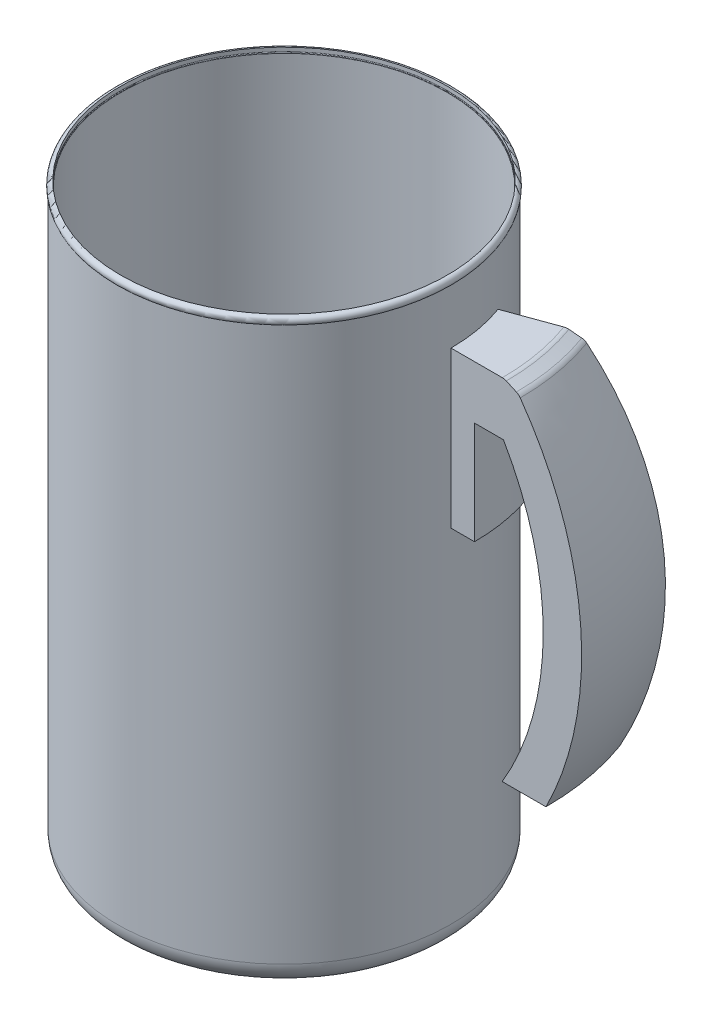
SolidWorks part; units mm, degrees
ref_plane "Front Plane" through (0, 0, 0) normal (0, 0, 1) x (1, 0, 0)
ref_plane "Top Plane" through (0, 0, 0) normal (0, 1, 0) x (1, 0, 0)
ref_plane "Right Plane" through (0, 0, 0) normal (1, 0, 0) x (0, 0, -1)
sketch "Sketch1" plane through (0, 0, 0) normal (0, 0, 1) x (1, 0, 0)
  line L0 (0, 0) -> (0, 316.8923) construction
  line L1 (0, 15.1909) -> (-75, 15.1909)
  line L2 (-85, 25.1909) -> (-85, 314.4808)
  line L3 (-85.1655, 314.6463) -> (-85.1844, 314.6463)
  line L4 (0, 15.1909) -> (0, 315.1909)
  line L5 (-85.1844, 315.1909) -> (0, 315.1909)
  arc A0 (-85.1844, 315.1909) -> (-85.1844, 314.6463) centre (-85.1844, 314.9186) ccw
  arc A1 (-85.1655, 314.6463) -> (-85, 314.4808) centre (-85.1655, 314.4808) cw
  arc A2 (-75, 15.1909) -> (-85, 25.1909) centre (-75, 25.1909) cw
  point P6 (-85.1821, 314.6461)
  dimension "D3" = 10
  dimension "D1" = 170
  dimension "D4" = 300
revolve "Revolve1" add sketch "Sketch1" angle 360 about L4
shell "Shell7" thickness 2 removed face at (0, 315.1909, -85.1844) outward yes
sketch "Sketch4" plane through (0, 0, 0) normal (0, 0, 1) x (1, 0, 0)
  line L0 (87, 285.1658) -> (113.7412, 285.1658)
  line L1 (87, 25.1909) -> (87, 313.5522) construction
  line L2 (115.793, 284.7255) -> (121.0361, 282.3661)
  line L3 (87, 203.914) -> (99.2279, 203.914)
  line L4 (99.2279, 203.914) -> (99.2279, 257.4468)
  line L5 (99.2279, 257.4468) -> (114.2959, 257.4468)
  line L6 (113.6555, 102.9267) -> (136.4617, 102.9267)
  line L7 (87, 285.1658) -> (87, 203.914)
  line L8 (0, 0) -> (0, 519.2789) construction
  arc A0 (123.0565, 280.7077) -> (136.4617, 102.9267) centre (-17.2717, 180.7307) cw
  arc A1 (114.2959, 257.4468) -> (113.6555, 102.9267) centre (-17.2717, 180.7307) cw
  arc A2 (123.0565, 280.7077) -> (121.0361, 282.3661) centre (118.9843, 277.8064) ccw
  arc A3 (115.793, 284.7255) -> (113.7412, 285.1658) centre (113.7412, 280.1658) ccw
  dimension "D1" = 20
  dimension "D2" = 5
  dimension "D3" = 5
revolve "Revolve2" add sketch "Sketch4" angle 20 about L8
